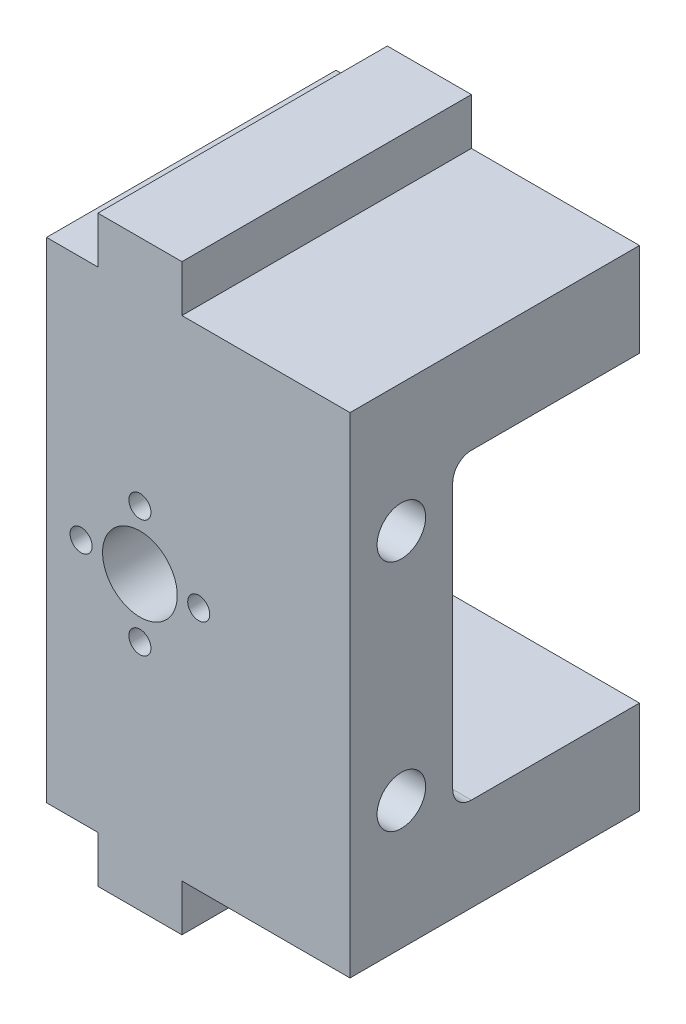
SolidWorks part; units mm, degrees
ref_plane "Front Plane" through (0, 0, 0) normal (0, 0, 1) x (1, 0, 0)
ref_plane "Top Plane" through (0, 0, 0) normal (0, 1, 0) x (1, 0, 0)
ref_plane "Right Plane" through (0, 0, 0) normal (1, 0, 0) x (0, 0, -1)
sketch "Sketch1" plane through (0, 0, 0) normal (0, 0, 1) x (1, 0, 0)
  line L0 (0, 0) -> (0, 39.6494) construction
  line L1 (-12.7, 33.2994) -> (-5.715, 33.2994)
  line L2 (-12.7, 33.2994) -> (-12.7, -33.2994)
  line L3 (-12.7, -33.2994) -> (-5.715, -33.2994)
  line L4 (28.575, 33.2994) -> (28.575, -33.2994)
  line L5 (0, 0) -> (28.575, 0) construction
  line L6 (5.715, -33.2994) -> (5.715, -39.6494)
  line L8 (-5.715, 33.2994) -> (-5.715, 39.6494)
  line L9 (-5.715, 39.6494) -> (5.715, 39.6494)
  line L10 (5.715, 33.2994) -> (5.715, 39.6494)
  line L11 (-5.715, -33.2994) -> (-5.715, -39.6494)
  line L12 (-5.715, -39.6494) -> (5.715, -39.6494)
  line L13 (5.715, 33.2994) -> (28.575, 33.2994)
  line L14 (5.715, -33.2994) -> (28.575, -33.2994)
  circle A0 centre (0, 0) radius 5.08
  circle A1 centre (0, 8.001) radius 1.5
  circle A2 centre (0, 0) radius 5.08
  circle A3 centre (8.001, 0) radius 1.5
  circle A4 centre (0, 0) radius 5.08
  circle A5 centre (0, -8.001) radius 1.5
  circle A6 centre (0, 0) radius 5.08
  circle A7 centre (-8.001, 0) radius 1.5
  point P15 (0, 39.6494)
  dimension "D5" = 10.16
  dimension "D9" = 3
  dimension "D1" = 33.2994
  dimension "D2" = 33.2994
  dimension "D3" = 12.7
  dimension "D4" = 28.575
  dimension "D6" = 11.43
  dimension "D7" = 6.35
  dimension "D8" = 8.001
  dimension "D10" = 4
extrude "Boss-Extrude1" add sketch "Sketch1" along normal blind 13.97
sketch "Sketch2" plane through (0, 0, 0) normal (0, 0, -1) x (-1, 0, 0)
  line L0 (8.001, -3.5796) -> (11.101, -1.7898)
  line L1 (3.5796, 8.001) -> (1.7898, 11.101)
  line L2 (1.7898, 11.101) -> (-1.7898, 11.101)
  line L3 (-1.7898, 11.101) -> (-3.5796, 8.001)
  line L4 (-3.5796, 8.001) -> (-1.7898, 4.901)
  line L5 (-1.7898, 4.901) -> (1.7898, 4.901)
  line L6 (1.7898, 4.901) -> (3.5796, 8.001)
  line L7 (11.101, -1.7898) -> (11.101, 1.7898)
  line L8 (11.101, 1.7898) -> (8.001, 3.5796)
  line L9 (8.001, 3.5796) -> (4.901, 1.7898)
  line L10 (4.901, 1.7898) -> (4.901, -1.7898)
  line L11 (4.901, -1.7898) -> (8.001, -3.5796)
  line L12 (-3.5796, -8.001) -> (-1.7898, -11.101)
  line L13 (-1.7898, -11.101) -> (1.7898, -11.101)
  line L14 (1.7898, -11.101) -> (3.5796, -8.001)
  line L15 (3.5796, -8.001) -> (1.7898, -4.901)
  line L16 (1.7898, -4.901) -> (-1.7898, -4.901)
  line L17 (-1.7898, -4.901) -> (-3.5796, -8.001)
  line L18 (-8.001, 3.5796) -> (-11.101, 1.7898)
  line L19 (-11.101, 1.7898) -> (-11.101, -1.7898)
  line L20 (-11.101, -1.7898) -> (-8.001, -3.5796)
  line L21 (-8.001, -3.5796) -> (-4.901, -1.7898)
  line L22 (-4.901, -1.7898) -> (-4.901, 1.7898)
  line L23 (-4.901, 1.7898) -> (-8.001, 3.5796)
  circle A0 centre (0, 8.001) radius 3.1 construction
  dimension "D1" = 6.2
  dimension "D2" = 4
extrude "Cut-Extrude1" cut sketch "Sketch2" against normal blind 3
fillet "Fillet1" radius 1.27 8 edges at (-4.901, -1.3366, 1.5) (-4.901, 1.3366, 1.5) (-1.3366, 4.901, 1.5) (1.3366, 4.901, 1.5) (4.901, 1.3366, 1.5) (4.901, -1.3366, 1.5) (1.3366, -4.901, 1.5) (-1.3366, -4.901, 1.5)
sketch "Sketch3" plane through (28.575, 0, 0) normal (1, 0, 0) x (0, 0, -1)
  line L0 (0, 0) -> (-13.97, 0) construction
  line L1 (-13.97, 33.2994) -> (-13.97, -33.2994) construction
  line L2 (-6.985, 0) -> (-6.985, 39.6494) construction
  line L3 (-13.97, 39.6494) -> (0, 39.6494) construction
  circle A0 centre (-6.985, 15.875) radius 3.302
  circle A1 centre (-6.985, -15.875) radius 3.302
  dimension "D1" = 6.604
  dimension "D2" = 15.875
extrude "Cut-Extrude2" cut sketch "Sketch3" against normal up to surface (41.275 mm away) up to face at (-12.7, 0, 6.985)
sketch "Sketch4" plane through (-12.7, 0, 0) normal (-1, 0, 0) x (0, 0, 1)
  line L0 (0, 0) -> (13.97, 0) construction
  line L1 (0, 33.2994) -> (0, -33.2994) construction
  line L2 (13.97, 33.2994) -> (13.97, -33.2994) construction
  line L3 (12.7, -19.1746) -> (6.985, -22.4741)
  line L4 (6.985, 22.4741) -> (1.27, 19.1746)
  line L5 (1.27, 19.1746) -> (1.27, 12.5754)
  line L6 (1.27, 12.5754) -> (6.985, 9.2759)
  line L7 (6.985, 9.2759) -> (12.7, 12.5754)
  line L8 (12.7, 12.5754) -> (12.7, 19.1746)
  line L9 (12.7, 19.1746) -> (6.985, 22.4741)
  line L10 (12.7, -12.5754) -> (12.7, -19.1746)
  line L11 (6.985, -9.2759) -> (12.7, -12.5754)
  line L12 (1.27, -12.5754) -> (6.985, -9.2759)
  line L13 (1.27, -19.1746) -> (1.27, -12.5754)
  line L14 (6.985, -22.4741) -> (1.27, -19.1746)
  circle A0 centre (6.985, 15.875) radius 5.715 construction
  circle A1 centre (6.985, -15.875) radius 5.715 construction
  dimension "D1" = 11.43
extrude "Cut-Extrude3" cut sketch "Sketch4" against normal blind 5.842
sketch "Sketch5" plane through (0, 0, 0) normal (0, 0, -1) x (-1, 0, 0)
  line L0 (-28.575, 20.5994) -> (12.7, 20.5994)
  line L1 (12.7, -20.5994) -> (-28.575, -20.5994)
  line L2 (12.7, 33.2994) -> (12.7, -33.2994) construction
  line L3 (-5.715, -33.2994) -> (-28.575, -33.2994) construction
  line L4 (-28.575, -20.5994) -> (-28.575, -33.2994)
  line L5 (12.7, 20.5994) -> (12.7, 33.2994)
  line L12 (-5.715, -33.2994) -> (-5.715, -39.6494)
  line L13 (-5.715, -39.6494) -> (5.715, -39.6494)
  line L14 (5.715, -39.6494) -> (5.715, -33.2994)
  line L15 (5.715, -33.2994) -> (12.7, -33.2994)
  line L16 (12.7, -33.2994) -> (12.7, 33.2994)
  line L17 (12.7, 33.2994) -> (5.715, 33.2994)
  line L18 (5.715, 33.2994) -> (5.715, 39.6494)
  line L19 (5.715, 39.6494) -> (-5.715, 39.6494)
  line L20 (-5.715, 39.6494) -> (-5.715, 33.2994)
  line L21 (-5.715, 33.2994) -> (-28.575, 33.2994)
  line L22 (-28.575, 33.2994) -> (-28.575, -33.2994)
  line L23 (-28.575, -33.2994) -> (-5.715, -33.2994)
  line L24 (-5.715, -33.2994) -> (-5.715, -39.6494)
  line L25 (-5.715, -39.6494) -> (5.715, -39.6494)
  line L26 (5.715, -39.6494) -> (5.715, -33.2994)
  line L27 (5.715, -33.2994) -> (12.7, -33.2994)
  line L28 (12.7, -33.2994) -> (12.7, -20.5994)
  line L29 (12.7, 33.2994) -> (5.715, 33.2994)
  line L30 (5.715, 33.2994) -> (5.715, 39.6494)
  line L31 (5.715, 39.6494) -> (-5.715, 39.6494)
  line L32 (-5.715, 39.6494) -> (-5.715, 33.2994)
  line L33 (-5.715, 33.2994) -> (-28.575, 33.2994)
  line L34 (-28.575, 33.2994) -> (-28.575, 20.5994)
  line L35 (-28.575, -33.2994) -> (-5.715, -33.2994)
  dimension "D2" = 12.7
  dimension "D3" = 12.7
  dimension "D1" = 0
extrude "Boss-Extrude2" add sketch "Sketch5" along normal blind 25.4
fillet "Fillet2" radius 2.54 2 edges at (7.9375, -20.5994, 0) (7.9375, 20.5994, 0)
equation "\"D2@Sketch1\"=\"D1@Sketch1\""
